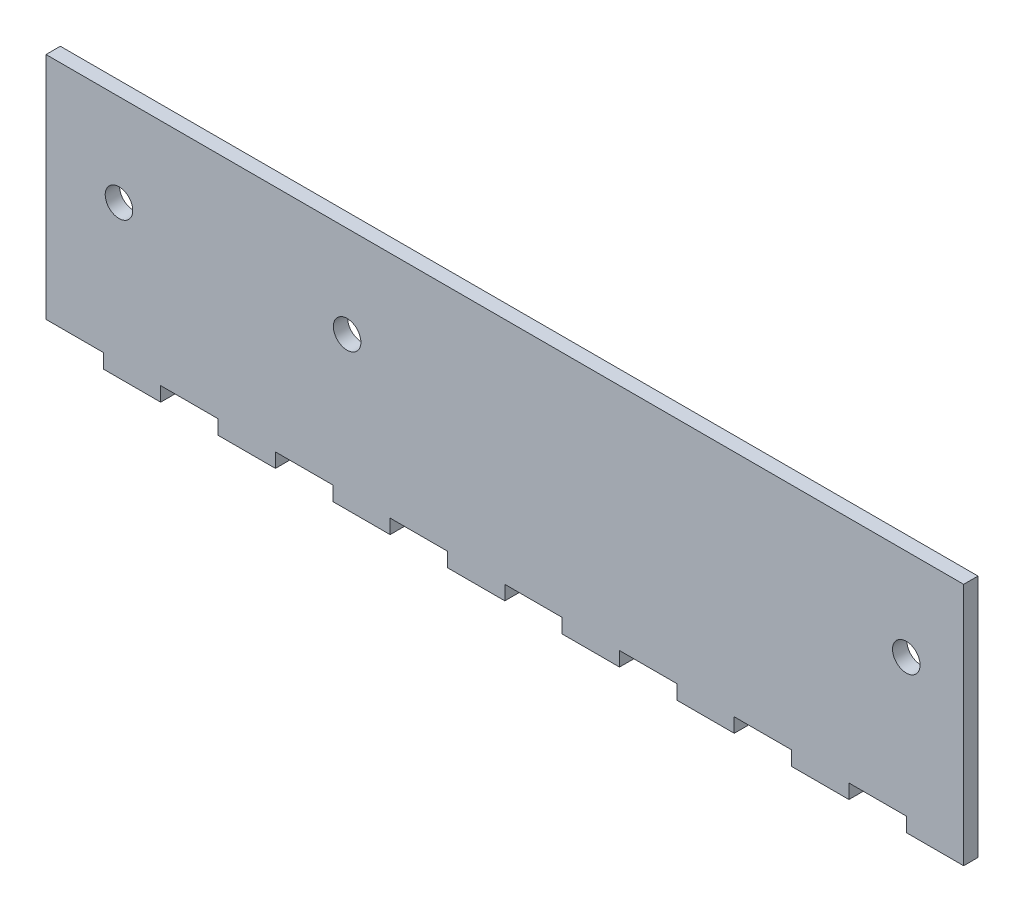
SolidWorks part; units mm, degrees
ref_plane "Front" through (0, 0, 0) normal (0, 0, 1) x (1, 0, 0)
ref_plane "Top" through (0, 0, 0) normal (0, 1, 0) x (1, 0, 0)
ref_plane "Right" through (0, 0, 0) normal (1, 0, 0) x (0, 0, -1)
sketch "Sketch1" plane through (0, 0, 0) normal (0, 0, 1) x (1, 0, 0)
  line L5 (0, 0) -> (203.2, 0)
  line L6 (0, 0) -> (0, 50.8)
  line L7 (0, 50.8) -> (203.2, 50.8)
  line L8 (203.2, 0) -> (203.2, 50.8)
  circle A0 centre (190.5, 30.48) radius 3.048
  circle A1 centre (66.675, 30.48) radius 3.048
  circle A2 centre (16.1608, 30.48) radius 3.048
  point P4 (0, 0)
  dimension "D7" = 6.096
  dimension "D8" = 6.096
  dimension "D9" = 6.096
  dimension "D1" = 203.2
  dimension "D2" = 50.8
  dimension "D3" = 50.5142
  dimension "D4" = 123.825
  dimension "D5" = 30.48
  dimension "D6" = 12.7
extrude "Boss-Extrude1" add sketch "Sketch1" along normal blind 3.175
sketch "Sketch2" plane through (0, 0, 0) normal (0, -1, 0) x (1, 0, 0)
  line L0 (0, 3.175) -> (203.2, 3.175) construction
  line L1 (203.2, 0) -> (190.5, 0)
  line L2 (203.2, 0) -> (203.2, 3.175)
  line L3 (203.2, 3.175) -> (190.5, 3.175)
  line L4 (190.5, 0) -> (190.5, 3.175)
  line L5 (177.8, 0) -> (177.8, 3.175)
  line L6 (177.8, 0) -> (165.1, 0)
  line L7 (165.1, 0) -> (165.1, 3.175)
  line L8 (177.8, 3.175) -> (165.1, 3.175)
  line L9 (152.4, 0) -> (152.4, 3.175)
  line L10 (152.4, 0) -> (139.7, 0)
  line L11 (139.7, 0) -> (139.7, 3.175)
  line L12 (152.4, 3.175) -> (139.7, 3.175)
  line L13 (127, 0) -> (127, 3.175)
  line L14 (127, 0) -> (114.3, 0)
  line L15 (114.3, 0) -> (114.3, 3.175)
  line L16 (127, 3.175) -> (114.3, 3.175)
  line L17 (101.6, 0) -> (101.6, 3.175)
  line L18 (101.6, 0) -> (88.9, 0)
  line L19 (88.9, 0) -> (88.9, 3.175)
  line L20 (101.6, 3.175) -> (88.9, 3.175)
  line L21 (76.2, 0) -> (76.2, 3.175)
  line L22 (76.2, 0) -> (63.5, 0)
  line L23 (63.5, 0) -> (63.5, 3.175)
  line L24 (76.2, 3.175) -> (63.5, 3.175)
  line L25 (50.8, 0) -> (50.8, 3.175)
  line L26 (50.8, 0) -> (38.1, 0)
  line L27 (38.1, 0) -> (38.1, 3.175)
  line L28 (50.8, 3.175) -> (38.1, 3.175)
  line L29 (25.4, 0) -> (25.4, 3.175)
  line L30 (25.4, 0) -> (12.7, 0)
  line L31 (12.7, 0) -> (12.7, 3.175)
  line L32 (25.4, 3.175) -> (12.7, 3.175)
  dimension "D1" = 12.7
  dimension "D2" = 8
extrude "Boss-Extrude2" add sketch "Sketch2" along normal blind 3.175
